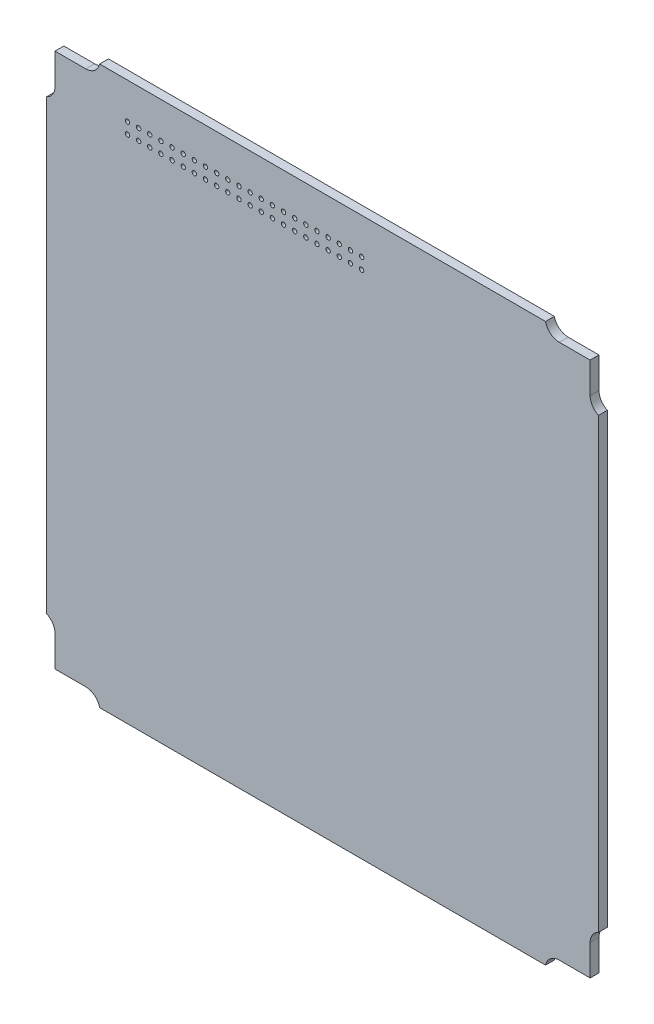
SolidWorks part; units mm, degrees
ref_plane "Front Plane" through (0, 0, 0) normal (0, 0, 1) x (1, 0, 0)
ref_plane "Top Plane" through (0, 0, 0) normal (0, 1, 0) x (1, 0, 0)
ref_plane "Right Plane" through (0, 0, 0) normal (1, 0, 0) x (0, 0, -1)
sketch "Sketch1" plane through (0, 0, 0) normal (0, 0, 1) x (1, 0, 0)
  line L0 (-40, 50) -> (-40, 48)
  line L1 (-50, -50) -> (50, -50)
  line L2 (-50, -50) -> (-50, 50)
  line L3 (-50, 50) -> (50, 50)
  line L4 (50, -50) -> (50, 50)
  line L5 (-50, -50) -> (50, 50) construction
  line L6 (-50, 50) -> (50, -50) construction
  line L7 (-50, 50) -> (-40, 50)
  line L8 (-50, 50) -> (-50, 40)
  line L9 (-40, 48) -> (-48, 48)
  line L10 (-48, 48) -> (-48, 40)
  line L11 (50, 50) -> (40, 50)
  line L12 (50, 50) -> (50, 40)
  line L13 (-48, 40) -> (-50, 40)
  line L14 (50, 40) -> (48, 40)
  line L15 (-50, -50) -> (-37.8649, -50)
  line L16 (-50, -50) -> (-50, -37.8649)
  line L17 (50, 50) -> (50, 40)
  line L18 (50, 50) -> (40, 50)
  line L19 (50, -50) -> (41.5, -50)
  line L20 (50, -50) -> (50, -41.5)
  line L21 (48, 40) -> (48, 48)
  line L22 (48, 48) -> (40, 48)
  line L23 (40, 48) -> (40, 50)
  line L24 (40, -50) -> (40, -48)
  line L25 (50, -50) -> (40, -50)
  line L26 (50, -50) -> (50, -40)
  line L27 (40, -48) -> (48, -48)
  line L28 (48, -48) -> (48, -40)
  line L29 (48, -40) -> (50, -40)
  line L30 (-50, -40) -> (-48, -40)
  line L31 (-50, -50) -> (-50, -40)
  line L32 (-50, -50) -> (-40, -50)
  line L33 (-48, -40) -> (-48, -48)
  line L34 (-48, -48) -> (-40, -48)
  line L35 (-40, -48) -> (-40, -50)
  point P0 (0, 0)
  point P38 (0, 0)
  dimension "D1" = 100
  dimension "D2" = 100
  dimension "D3" = 2
  dimension "D4" = 10
  dimension "D5" = 4
extrude "Boss-Extrude1" add sketch "Sketch1" along normal blind 1.5875 contours L1 L4 L3 L2 region at (0, 0, 0)
fillet "Fillet1" radius 2.54 8 edges at (-48, -40, 0.7937) (-40, -48, 0.7937) (40, -48, 0.7937) (48, -40, 0.7937) (48, 40, 0.7937) (40, 48, 0.7937) (-40, 48, 0.7937) (-48, 40, 0.7937)
sketch "Sketch5" plane through (0, 0, 1.5875) normal (0, 0, 1) x (1, 0, 0)
  line L0 (0, 50) -> (0, -50) construction
  line L5 (-40, 50) -> (40, 50) construction
  line L6 (-40, -50) -> (40, -50) construction
  line L8 (-35.7478, 50) -> (8.2522, 50) construction
  line L9 (-35.7478, 50) -> (-35.7478, 45.8) construction
  line L10 (-35.7478, 45.8) -> (8.2522, 45.8) construction
  line L11 (8.2522, 50) -> (8.2522, 45.8) construction
  circle A0 centre (-35, 43.55) radius 0.395
  circle A1 centre (-33, 43.55) radius 0.395
  circle A2 centre (-31, 43.55) radius 0.395
  circle A3 centre (-29, 43.55) radius 0.395
  circle A4 centre (-27, 43.55) radius 0.395
  circle A5 centre (-25, 43.55) radius 0.395
  circle A6 centre (-23, 43.55) radius 0.395
  circle A7 centre (-21, 43.55) radius 0.395
  circle A8 centre (-19, 43.55) radius 0.395
  circle A9 centre (-17, 43.55) radius 0.395
  circle A10 centre (-15, 43.55) radius 0.395
  circle A11 centre (-13, 43.55) radius 0.395
  circle A12 centre (-11, 43.55) radius 0.395
  circle A13 centre (-9, 43.55) radius 0.395
  circle A14 centre (-7, 43.55) radius 0.395
  circle A15 centre (-5, 43.55) radius 0.395
  circle A16 centre (-3, 43.55) radius 0.395
  circle A17 centre (-1, 43.55) radius 0.395
  circle A18 centre (1, 43.55) radius 0.395
  circle A19 centre (3, 43.55) radius 0.395
  circle A20 centre (5, 43.55) radius 0.395
  circle A21 centre (7, 43.55) radius 0.395
  circle A22 centre (-33, 41.55) radius 0.395
  circle A23 centre (-31, 41.55) radius 0.395
  circle A24 centre (-29, 41.55) radius 0.395
  circle A25 centre (-27, 41.55) radius 0.395
  circle A26 centre (-25, 41.55) radius 0.395
  circle A27 centre (-23, 41.55) radius 0.395
  circle A28 centre (-21, 41.55) radius 0.395
  circle A29 centre (-19, 41.55) radius 0.395
  circle A30 centre (-17, 41.55) radius 0.395
  circle A31 centre (-15, 41.55) radius 0.395
  circle A32 centre (-13, 41.55) radius 0.395
  circle A33 centre (-11, 41.55) radius 0.395
  circle A34 centre (-9, 41.55) radius 0.395
  circle A35 centre (-7, 41.55) radius 0.395
  circle A36 centre (-5, 41.55) radius 0.395
  circle A37 centre (-3, 41.55) radius 0.395
  circle A38 centre (-1, 41.55) radius 0.395
  circle A39 centre (1, 41.55) radius 0.395
  circle A40 centre (3, 41.55) radius 0.395
  circle A41 centre (5, 41.55) radius 0.395
  circle A42 centre (7, 41.55) radius 0.395
  circle A43 centre (-35, 41.55) radius 0.395
  dimension "D5" = 0.79
  dimension "D2" = 2.25
  dimension "D3" = 2
  dimension "D4" = 2
  dimension "D8" = 1
  dimension "D9" = 44
  dimension "D10" = 4.2
  dimension "D6" = 22
  dimension "D7" = 2
extrude "Cut-Extrude1" cut sketch "Sketch5" against normal through all
sketch "Sketch6" plane through (0, 0, 1.5875) normal (0, 0, 1) x (1, 0, 0)
  line L0 (-40, 50) -> (40, 50) construction
  line L1 (-49.5, 50) -> (49.5, 50)
  line L2 (-49.5, 50) -> (-49.5, -50)
  line L3 (-49.5, -50) -> (49.5, -50)
  line L4 (49.5, 50) -> (49.5, -50)
  line L5 (-40, -50) -> (40, -50) construction
  line L6 (50, -40) -> (50, 40) construction
  dimension "D1" = 99
  dimension "D2" = 0.5
extrude "Cut-Extrude2" cut sketch "Sketch6" against normal through all flip side to cut
sketch "Sketch2" plane through (0, 0, 1.5875) normal (0, 0, 1) x (1, 0, 0)
  line L0 (-36.5, 41) -> (36.5, 41)
  line L1 (-39, 38.5) -> (-36.5, 41)
  line L2 (39, 38.5) -> (39, 26.5)
  line L3 (36.5, 24) -> (-36.5, 24)
  line L4 (-39, 26.5) -> (-39, 38.5)
  line L5 (-36.5, 24) -> (-39, 26.5)
  line L6 (0, 0) -> (0, 50) construction
  line L7 (36.5, 41) -> (39, 38.5)
  line L8 (39, 26.5) -> (36.5, 24)
  line L9 (-36.5, 22.75) -> (36.5, 22.75)
  line L10 (-39, 20.25) -> (-36.5, 22.75)
  line L11 (39, 20.25) -> (39, 8.25)
  line L12 (36.5, 5.75) -> (-36.5, 5.75)
  line L13 (-39, 8.25) -> (-39, 20.25)
  line L14 (-36.5, 5.75) -> (-39, 8.25)
  line L15 (36.5, 22.75) -> (39, 20.25)
  line L16 (39, 8.25) -> (36.5, 5.75)
  line L17 (-36.5, 4.5) -> (36.5, 4.5)
  line L18 (-39, 2) -> (-36.5, 4.5)
  line L19 (39, 2) -> (39, -10)
  line L20 (36.5, -12.5) -> (-36.5, -12.5)
  line L21 (-39, -10) -> (-39, 2)
  line L22 (-36.5, -12.5) -> (-39, -10)
  line L23 (36.5, 4.5) -> (39, 2)
  line L24 (39, -10) -> (36.5, -12.5)
  line L25 (-36.5, -13.75) -> (36.5, -13.75)
  line L26 (-39, -16.25) -> (-36.5, -13.75)
  line L27 (39, -16.25) -> (39, -28.25)
  line L28 (36.5, -30.75) -> (-36.5, -30.75)
  line L29 (-39, -28.25) -> (-39, -16.25)
  line L30 (-40, 50) -> (40, 50) construction
  line L33 (-36.5, -30.75) -> (-39, -28.25)
  line L34 (36.5, -13.75) -> (39, -16.25)
  line L36 (39, -28.25) -> (36.5, -30.75)
  line L37 (-36.5, -32) -> (36.5, -32)
  line L38 (-39, -34.5) -> (-36.5, -32)
  line L39 (39, -34.5) -> (39, -46.5)
  line L40 (36.5, -49) -> (-36.5, -49)
  line L41 (-39, -46.5) -> (-39, -34.5)
  line L42 (-36.5, -49) -> (-39, -46.5)
  line L43 (36.5, -32) -> (39, -34.5)
  line L44 (39, -46.5) -> (36.5, -49)
  line L45 (-40, -50) -> (40, -50) construction
  point P0 (-39, 41)
  point P3 (39, 41)
  point P4 (39, 24)
  point P5 (-39, 24)
  point P19 (-39, 22.75)
  point P21 (39, 22.75)
  point P22 (39, 5.75)
  point P23 (-39, 5.75)
  point P31 (-39, 4.5)
  point P33 (39, 4.5)
  point P34 (39, -12.5)
  point P35 (-39, -12.5)
  point P43 (-39, -13.75)
  point P45 (39, -13.75)
  point P46 (39, -30.75)
  point P47 (-39, -30.75)
  point P55 (-39, -32)
  point P57 (39, -32)
  point P58 (39, -49)
  point P59 (-39, -49)
  dimension "D1" = 78
  dimension "D2" = 17
  dimension "D3" = 5
  dimension "D4" = 1
  dimension "D5" = 9
